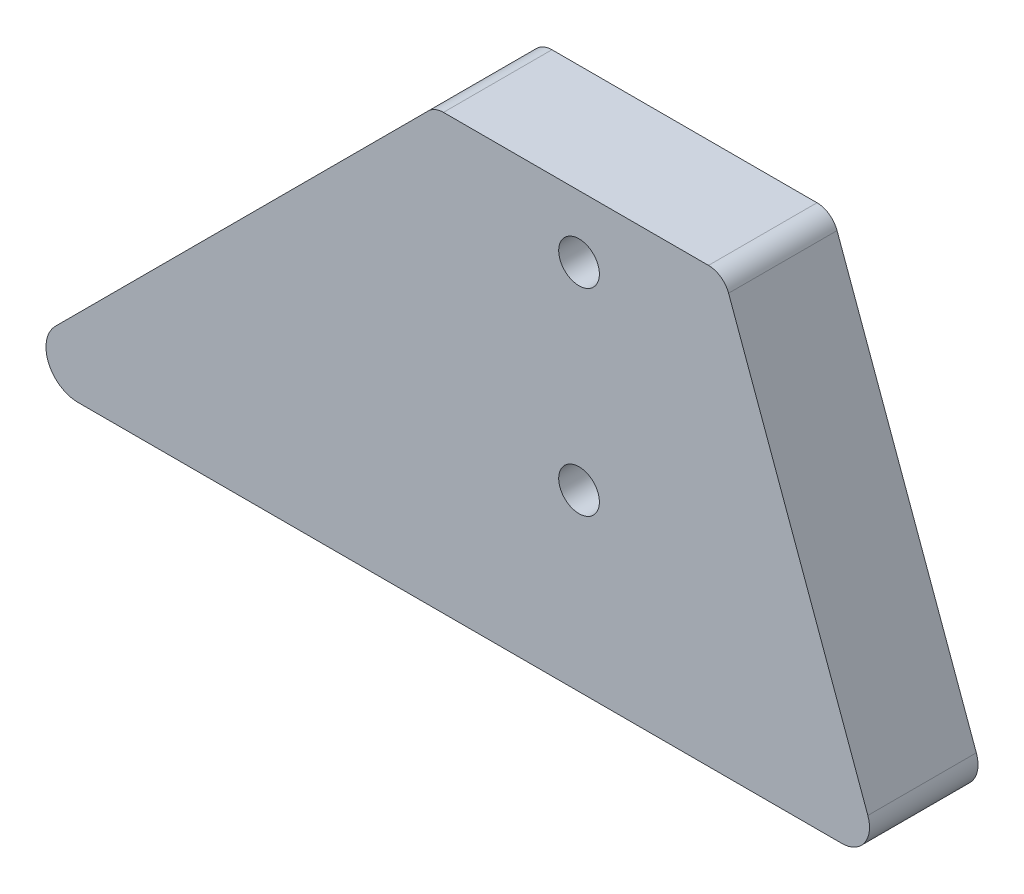
SolidWorks part; units mm, degrees
material "6061 Alloy"
ref_plane "Front Plane" through (0, 0, 0) normal (0, 0, 1) x (1, 0, 0)
ref_plane "Top Plane" through (0, 0, 0) normal (0, 1, 0) x (1, 0, 0)
ref_plane "Right Plane" through (0, 0, 0) normal (1, 0, 0) x (0, 0, -1)
sketch "Sketch1" plane through (0, 0, 0) normal (0, 0, 1) x (1, 0, 0)
  line L3 (9.525, 35.738) -> (-38.1, 35.738)
  line L5 (-38.1, 35.738) -> (-38.1, -65.862)
  line L6 (-38.1, -65.862) -> (9.525, -65.862)
  line L7 (9.525, 35.738) -> (9.525, -65.862)
  line L8 (-38.1, 35.738) -> (-46.0289, 35.738)
  line L9 (-49.5645, 34.2735) -> (-136.8967, -53.0587)
  line L10 (-131.5934, -65.862) -> (-38.1, -65.862)
  line L11 (9.525, 35.738) -> (16.024, 35.738)
  line L12 (20.7224, 32.4481) -> (53.3294, -57.1389)
  line L13 (47.2214, -65.862) -> (9.525, -65.862)
  line L14 (0, 0) -> (0, -25)
  line L15 (0, -25) -> (-14.2875, -25)
  line L16 (-14.2875, -65.862) -> (-14.2875, -25)
  line L17 (-14.2875, -25) -> (-14.2875, 21.21)
  arc A2 (-46.0289, 35.738) -> (-49.5645, 34.2735) centre (-46.0289, 30.738) ccw
  arc A3 (20.7224, 32.4481) -> (16.024, 35.738) centre (16.024, 30.738) ccw
  arc A4 (-131.5934, -65.862) -> (-136.8967, -53.0587) centre (-131.5934, -58.362) cw
  arc A5 (47.2214, -65.862) -> (53.3294, -57.1389) centre (47.2214, -59.362) ccw
  circle A6 centre (-14.2875, -25) radius 4.7625
  circle A7 centre (-14.2875, 21.21) radius 4.7625
  point P16 (-48.1, 35.738)
  point P19 (19.525, 35.738)
  dimension "D3" = 46.21
  dimension "D4" = 25
  dimension "D11" = 5
  dimension "D12" = 5
  dimension "D13" = 7.5
  dimension "D14" = 6.5
  dimension "D5" = 9.525
  dimension "D6" = 47.625
  dimension "D16" = 9.525
  dimension "D2" = 101.6
  dimension "D7" = 10
  dimension "D8" = 45
  dimension "D9" = 10
  dimension "D10" = 70
  dimension "D15" = 14.2875
  dimension "D17" = 40.862
extrude "Boss-Extrude1" add sketch "Sketch1" along normal blind 12.7 and the other way blind 12.7 contours L13 A5 L12 A3 L11 L7 | A7 A6 L6 L7 L3 L5 | A4 L10 L5 L8 A2 L9 region at (8.4029, -15.062, 0) region at (25.5837, -25.8392, 0) region at (-74.8242, -28.8366, 0)
